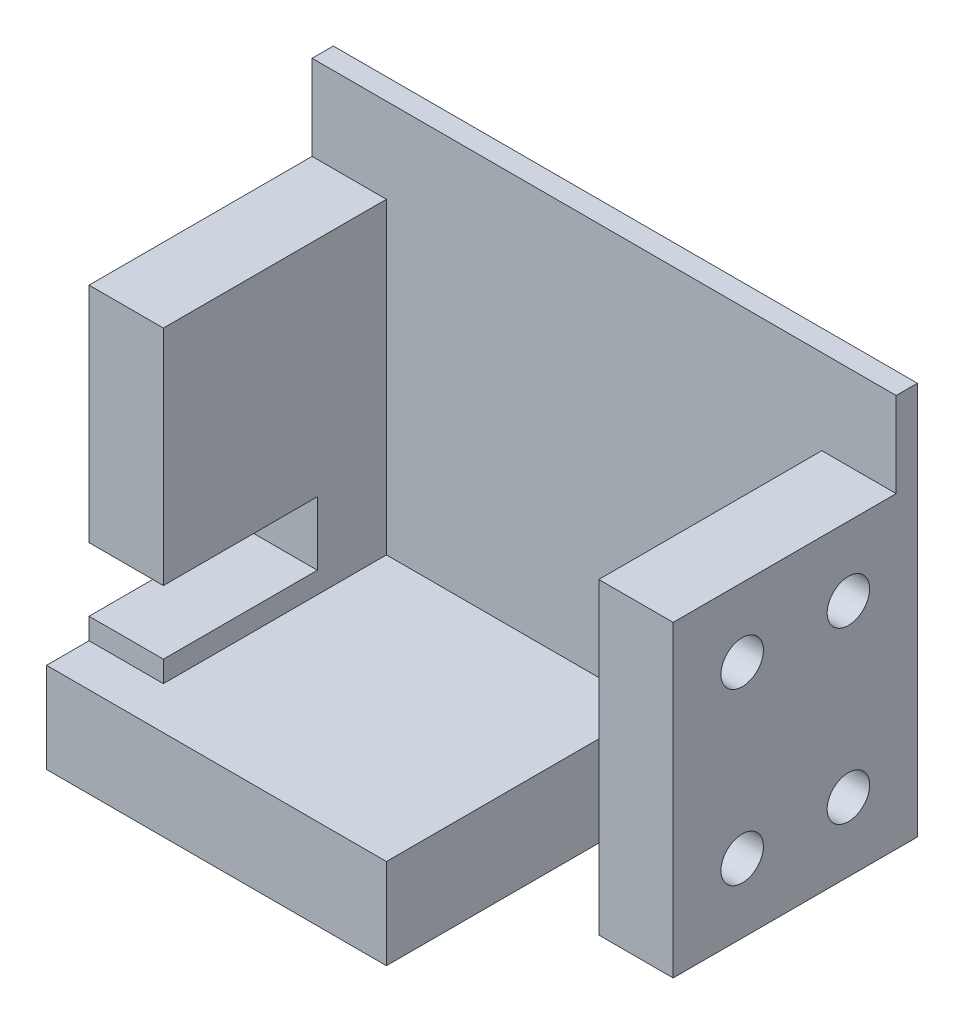
SolidWorks part; units mm, degrees
ref_plane "Front Plane" through (0, 0, 0) normal (0, 0, 1) x (1, 0, 0)
ref_plane "Top Plane" through (0, 0, 0) normal (0, 1, 0) x (1, 0, 0)
ref_plane "Right Plane" through (0, 0, 0) normal (1, 0, 0) x (0, 0, -1)
sketch "Sketch1" plane through (0, 0, 0) normal (0, 0, 1) x (1, 0, 0)
  line L0 (-4.3312, 34.7958) -> (-4.3312, -2.2042) construction
  line L1 (-31.8312, 34.7958) -> (23.1688, 34.7958)
  line L2 (-31.8312, 34.7958) -> (-31.8312, -2.2042)
  line L3 (-31.8312, -2.2042) -> (23.1688, -2.2042)
  line L4 (23.1688, 34.7958) -> (23.1688, -2.2042)
  line L5 (-31.8312, -2.2042) -> (-24.8312, -2.2042)
  line L6 (-31.8312, -2.2042) -> (-31.8312, 26.7958)
  line L7 (-31.8312, 26.7958) -> (-24.8312, 26.7958)
  line L8 (-24.8312, -2.2042) -> (-24.8312, 26.7958)
  line L9 (23.1688, 26.7958) -> (16.1688, 26.7958)
  line L10 (16.1688, -2.2042) -> (16.1688, 26.7958)
  dimension "D1" = 37
  dimension "D2" = 55
  dimension "D3" = 29
  dimension "D4" = 7
extrude "Sides" add sketch "Sketch1" along normal blind 23 contours L3 L8 L7 L2 | L10 L3 L4 L9 region at (-28.3312, 12.2958, 0) region at (19.6688, 12.2958, 0)
extrude "Back Plate" add sketch "Sketch1<3>" along normal blind 2 contours L0 L1 L2 L7 L8 L3 | L1 L0 L3 L10 L9 L4 region at (6.8641, 17.2928, 0) region at (-15.5266, 17.2928, 0)
sketch "Sketch1<3>" plane through (0, 0, 0) normal (0, 0, 1) x (1, 0, 0) same geometry as "Sketch1"
sketch "Sketch2" plane through (0, -2.2042, 0) normal (0, -1, 0) x (1, 0, 0)
  line L0 (-31.8312, 11) -> (0.1688, 11) construction
  line L1 (-31.8312, 0) -> (-11.8312, 0)
  line L2 (-31.8312, 0) -> (-31.8312, 23)
  line L5 (-15.8312, 27) -> (-15.8312, -5) construction
  line L7 (-31.8312, 27) -> (0.1688, 27)
  line L8 (-31.8312, 27) -> (-31.8312, -5)
  line L9 (-31.8312, -5) -> (0.1688, -5)
  line L10 (0.1688, 27) -> (0.1688, -5)
  circle A0 centre (-15.8312, 11) radius 3.75
  circle A1 centre (-15.8312, 11) radius 11.25
  point P8 (0, 0)
  point P16 (-15.8312, 11)
  line M1 (-31.8312, 0) -> (23.1688, 0)
  line M5 (16.1688, 2) -> (-24.8312, 2)
  line M6 (-24.8312, 2) -> (-24.8312, 23)
  line M7 (-24.8312, 23) -> (-31.8312, 23)
  line M8 (-31.8312, 23) -> (-31.8312, 0)
  dimension "D3" = 7.5
  dimension "D4" = 22.5
  dimension "D1" = 11
  dimension "D2" = 16
  dimension "D5" = 32
  dimension "D6" = 32
extrude "Bearing Base" add sketch "Sketch2" along normal blind 1 contours A1 L10 M6 M7 M8 M1 M5 | A1 L10 L7 L8 M6 M5 M7 | A1 A0 M6 | A0 | A1 M6 | A1 M6 M5 | L1 A1 M5 | A1 L10 M1 M5 region at (-28.3839, -2.2042, 10.9909) region at (-15.8312, -2.2042, 1.139) region at (-31.4252, -2.2042, 25) region at (-5.4096, -2.2042, 0.9373) region at (-24.1172, -2.2042, 2.7141) region at (-23.5837, -2.2042, 3.2475) region at (-25.7394, -2.2042, 11) region at (-15.8312, -2.2042, 11)
sketch "Sketch3" plane through (-31.8312, 0, 0) normal (-1, 0, 0) x (0, 0, 1)
  line L0 (23, 26.7958) -> (23, -2.2042) construction
  line L1 (23, 5.7958) -> (8.5, 5.7958)
  line L2 (23, 5.7958) -> (23, -0.2042)
  line L3 (23, -0.2042) -> (8.5, -0.2042)
  line L4 (8.5, 5.7958) -> (8.5, -0.2042)
  line L5 (23, 26.7958) -> (2, 26.7958) construction
  dimension "D1" = 6
  dimension "D2" = 14.5
  dimension "D3" = 21
extrude "Wire" cut sketch "Sketch3" against normal blind 21
sketch "Mid" plane through (0, 0, 0) normal (0, 0, 1) x (1, 0, 0)
  line L0 (-4.3312, 34.7958) -> (-4.3312, -2.2042) construction
  line L1 (-31.8312, 34.7958) -> (23.1688, 34.7958) construction
  line L2 (0.1688, -2.2042) -> (23.1688, -2.2042) construction
  line L3 (23.1688, 16.2958) -> (-31.8312, 16.2958) construction
  line L4 (23.1688, 34.7958) -> (23.1688, -2.2042) construction
  line L5 (-31.8312, 34.7958) -> (-31.8312, -3.2042) construction
extrude "Bearing" add sketch "Sketch2<4>" along normal blind 7.5 from offset 1 contours A1 L10 M6 M7 M8 M1 M5 | A1 L10 L7 L8 M6 M5 M7 | A1 L10 M1 M5 | A1 M6 M5 region at (-28.3839, -2.2042, 10.9909) region at (-31.4252, -2.2042, 25) region at (-5.4096, -2.2042, 0.9373) region at (-24.1172, -2.2042, 2.7141)
sketch "Sketch2<4>" plane through (0, -2.2042, 0) normal (0, -1, 0) x (1, 0, 0) same geometry as "Sketch2"
sketch "Moutning Holes" plane through (23.1688, 0, 0) normal (1, 0, 0) x (0, 0, -1)
  line L0 (-23, 12.2958) -> (0, 12.2958) construction
  line L1 (-23, 26.7958) -> (-23, -2.2042) construction
  line L2 (0, 34.7958) -> (0, -2.2042) construction
  line L3 (-11.5, -2.2042) -> (-11.5, 26.7958) construction
  line L4 (-23, -2.2042) -> (0, -2.2042) construction
  line L5 (-23, 26.7958) -> (-2, 26.7958) construction
  circle A0 centre (-16.5, 20.2958) radius 2
  circle A4 centre (-16.5, 20.2958) radius 4
  circle A5 centre (-6.5, 20.2958) radius 2
  circle A6 centre (-6.5, 20.2958) radius 4
  circle A7 centre (-16.5, 4.2958) radius 2
  circle A8 centre (-16.5, 4.2958) radius 4
  circle A9 centre (-6.5, 4.2958) radius 4
  circle A10 centre (-6.5, 4.2958) radius 2
  dimension "D1" = 4
  dimension "D4" = 8
  dimension "D2" = 5
  dimension "D3" = 8
extrude "Screw Holes" cut sketch "Moutning Holes" against normal blind 10 contours A10 | A7 | A0 | A5 region at (23.1688, 20.2958, 16.5) region at (23.1688, 20.2958, 6.5) region at (23.1688, 4.2958, 16.5) region at (23.1688, 4.2958, 6.5)
extrude "Screw Heads" cut sketch "Moutning Holes<3>" along normal blind 2.5 from surface contours A9 A10 | A8 A7 | A4 A0 | A6 A5 region at (23.1688, 20.2958, 20.3869) region at (23.1688, 20.2958, 10.3869) region at (23.1688, 4.2958, 20.3869) region at (23.1688, 4.2958, 10.3869) starting at face at (16.1688, 2.2958, 16.5)
sketch "Moutning Holes<3>" plane through (23.1688, 0, 0) normal (1, 0, 0) x (0, 0, -1) same geometry as "Moutning Holes"
